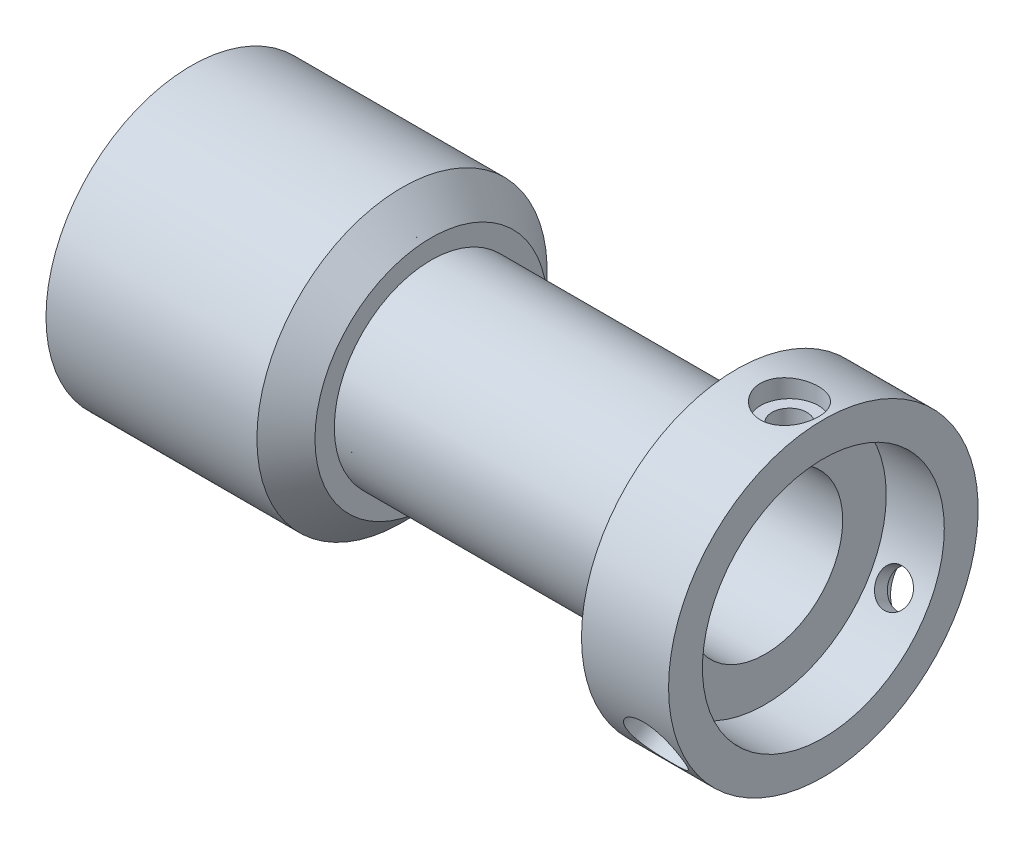
SolidWorks part; units mm, degrees
ref_plane "前视基准面" through (0, 0, 0) normal (0, 0, 1) x (1, 0, 0)
ref_plane "上视基准面" through (0, 0, 0) normal (0, 1, 0) x (1, 0, 0)
ref_plane "右视基准面" through (0, 0, 0) normal (1, 0, 0) x (0, 0, -1)
sketch "草图1" plane through (0, 0, 0) normal (0, 1, 0) x (1, 0, 0)
  line L0 (-27.6735, 0) -> (47.6327, 0) construction
  line L1 (0, 0) -> (0, 15)
  line L2 (0, 15) -> (24.8, 15)
  line L3 (24.8, 15) -> (24.8, 10)
  line L4 (24.8, 10) -> (56.35, 10)
  line L5 (56.35, 10) -> (56.35, 16)
  line L6 (56.35, 16) -> (65.35, 16)
  line L7 (65.35, 16) -> (65.35, 0)
  line L8 (65.35, 0) -> (0, 0)
  dimension "D1" = 15
  dimension "D2" = 16
  dimension "D3" = 24.8
  dimension "D4" = 9
  dimension "D5" = 65.35
  dimension "D6" = 5
revolve "旋转1" add sketch "草图1" angle 360 about L0
sketch "草图2" plane through (0, 0, 0) normal (-1, 0, 0) x (0, 0, 1)
  circle A0 centre (0, 0) radius 8
  dimension "D1" = 16
extrude "切除-拉伸1" cut sketch "草图2" against normal through all contours A0
ref_axis "基准轴1" through (65.35, 0, 0) along (-1, 0, 0)
sketch "草图5" plane through (65.35, 0, 0) normal (1, 0, 0) x (0, 0, -1)
  circle A0 centre (0, 0) radius 12.5
  dimension "D1" = 25
extrude "切除-拉伸2" cut sketch "草图5" against normal blind 6
chamfer "倒角1" distance 3 angle 45 1 edges at (24.8, 0, 15)
hole_wizard "M4 螺纹孔1" positions "草图12" profile "草图11" tap size "M4" standard "GB"
sketch "草图12" plane through (0, 0, 0) normal (-1, 0, 0) x (0, 0, 1)
  line L1 (0, 0) -> (0, 18.1631) construction
  circle A1 centre (0, 0) radius 11.25 construction
  point P0 (0, 11.25)
  dimension "D1" = 22.5
cosmetic thread "孔螺蚊线1" parameters "D1"=5, "D2"=4
sketch "草图11" plane through (0, 11.25, 0) normal (0, 1, 0) x (0, 0, 1)
  line L0 (0, 0) -> (0, 8.0914)
  line L1 (0, 8.0914) -> (1.65, 7.1)
  line L2 (1.65, 7.1) -> (1.65, 0)
  line L5 (1.65, 0) -> (0, 0)
  line L10 (0, 8.0914) -> (-1.65, 7.1) construction
  line L11 (0, -6.35) -> (0, 107.95) construction
  dimension "螺纹孔钻头直径" = 3.3
  dimension "螺纹孔钻头深度" = 7.1
  dimension "导头角度" = 118
pattern_circular "阵列(圆周)3" count 8 over 360 about axis through (65.35, 0, 0) along (-1, 0, 0) of "M4 螺纹孔1"
ref_plane "基准面1" through (0, 16, 0) normal (0, 1, 0) x (1, 0, 0)
hole_wizard "打孔尺寸(%根据)内六角圆柱头螺钉的类型1" positions "草图14" profile "草图13" counterbore size "M3" standard "GB" end condition up to next
sketch "草图14" plane through (0, 16, 0) normal (0, 1, 0) x (1, 0, 0)
  line L0 (61.85, 21.3179) -> (61.85, -19.3282) construction
  line L2 (56.35, 16) -> (56.35, -16) construction
  line L3 (0, 0) -> (76.8475, 0) construction
  line L4 (65.35, 0) -> (0, 0) construction
  point P0 (61.85, 0)
  dimension "D1" = 5.5
sketch "草图13" plane through (61.85, 16, 0) normal (1, 0, 0) x (0, 0, 1)
  line L0 (0, 0) -> (0, 32)
  line L1 (0, 32) -> (1.8, 32)
  line L3 (1.8, 32) -> (1.8, 2)
  line L4 (1.8, 2) -> (3, 2)
  line L5 (3, 2) -> (3, 0)
  line L7 (3, 0) -> (0, 0)
  line L11 (0, -6.35) -> (0, 107.95) construction
  dimension "通孔孔直径" = 3.6
  dimension "通孔孔深度" = 32
  dimension "柱形沉头孔直径" = 6
  dimension "柱形沉头孔深度" = 2
pattern_circular "阵列(圆周)4" count 3 over 360 about axis through (65.35, 0, 0) along (-1, 0, 0) of "打孔尺寸(%根据)内六角圆柱头螺钉的类型1"
